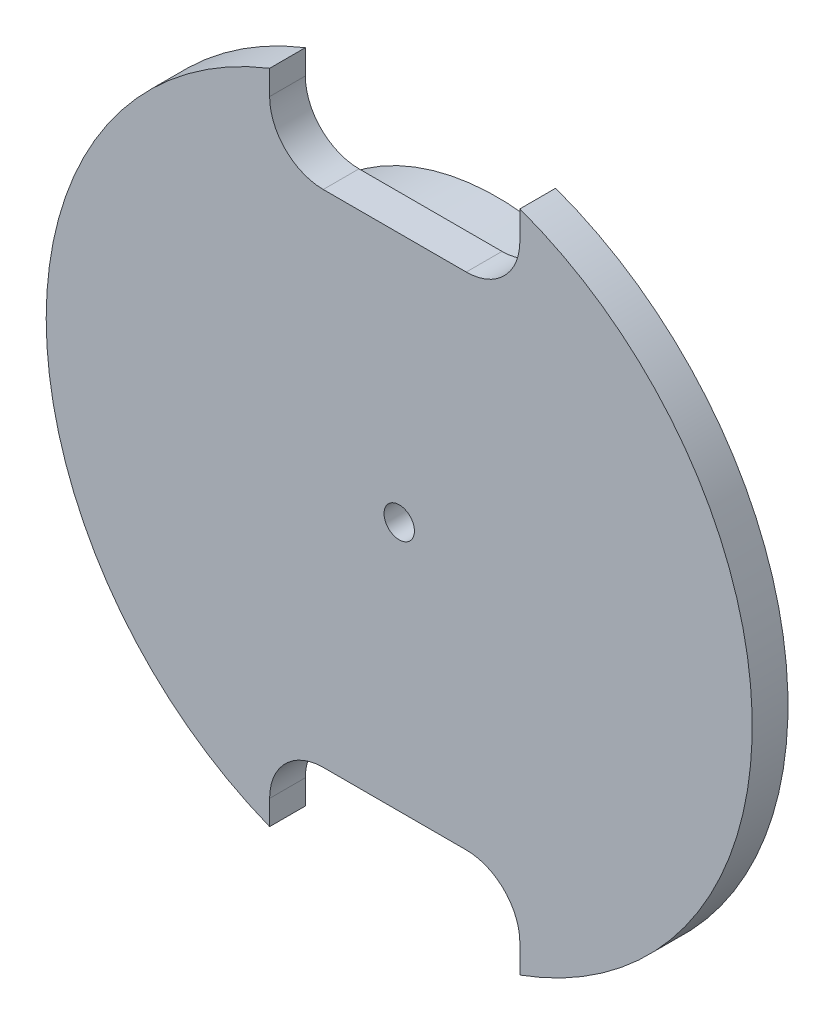
SolidWorks part; units mm, degrees
ref_plane "Płaszczyzna przednia" through (0, 0, 0) normal (0, 0, 1) x (1, 0, 0)
ref_plane "Płaszczyzna górna" through (0, 0, 0) normal (0, 1, 0) x (1, 0, 0)
ref_plane "Płaszczyzna prawa" through (0, 0, 0) normal (1, 0, 0) x (0, 0, -1)
sketch "Sketch1" plane through (0, 0, 0) normal (0, 0, 1) x (1, 0, 0)
  circle A0 centre (-12.8255, 19.2383) radius 39.5
extrude "Boss-Extrude1" add sketch "Sketch1" along normal blind 4
sketch "Sketch3" plane through (0, 0, 4) normal (0, 0, 1) x (1, 0, 0)
  circle A0 centre (-12.8255, 19.2383) radius 35
sketch "Sketch6" plane through (0, 0, 4) normal (0, 0, 1) x (1, 0, 0)
  line L0 (-12.8255, 54.2383) -> (-12.8255, -15.7617)
  line L1 (-47.8255, 19.2383) -> (22.1745, 19.2383)
  circle A0 centre (-12.8255, 19.2383) radius 35 construction
sketch "Sketch5" plane through (0, 0, 4) normal (0, 0, 1) x (1, 0, 0)
  line L0 (-21.3255, 59.2383) -> (-5.3255, 59.2383)
  line L1 (-21.3255, -8.7617) -> (-5.3255, -8.7617)
  line L2 (-21.3255, -8.7617) -> (-21.3255, -20.7617)
  line L3 (-21.3255, -20.7617) -> (-5.3255, -20.7617)
  line L4 (-5.3255, -8.7617) -> (-5.3255, -20.7617)
  line L5 (-21.3255, 59.2383) -> (-21.3255, 47.2383)
  line L6 (-21.3255, 47.2383) -> (-5.3255, 47.2383)
  line L7 (-5.3255, 59.2383) -> (-5.3255, 47.2383)
  line L17 (-12.8255, 54.2383) -> (-12.8255, -15.7617) construction
  line L22 (-27.3255, -14.7617) -> (-27.3255, -23.8497)
  line L23 (-27.3255, -23.8497) -> (0.6745, -23.8497)
  line L24 (0.6745, -23.8497) -> (0.6745, -14.7617)
  line L25 (0.6745, -14.7617) -> (-27.3255, -14.7617)
  line L30 (-27.3255, 53.2383) -> (-27.3255, 65.055)
  line L31 (-27.3255, 65.055) -> (0.6745, 65.055)
  line L32 (0.6745, 65.055) -> (0.6745, 53.2383)
  line L33 (0.6745, 53.2383) -> (-27.3255, 53.2383)
  arc A0 (-5.3255, -8.7617) -> (-5.3255, -20.7617) centre (-5.3255, -14.7617) cw
  arc A1 (-21.3255, -8.7617) -> (-21.3255, -20.7617) centre (-21.3255, -14.7617) ccw
  arc A2 (-5.3255, 59.2383) -> (-5.3255, 47.2383) centre (-5.3255, 53.2383) cw
  arc A3 (-21.3255, 59.2383) -> (-21.3255, 47.2383) centre (-21.3255, 53.2383) ccw
  circle A8 centre (-12.8255, 19.2383) radius 39.5 construction
  dimension "D1" = 16
  dimension "D2" = 12
  dimension "D3" = 16
  dimension "D4" = 12
  dimension "D10" = 40
  dimension "D12" = 40
  dimension "D13" = 7.5
  dimension "D15" = 7.5
extrude "Cut-Extrude2" cut sketch "Sketch5" against normal blind 10 contours A2 L7 | L5 A3 | L2 A1 | L4 L1 L2 L3 | A0 L4 | L7 L33 L5 L6 | L33 L30 L31 L32 | L25 L22 L23 L24 region at (-13.3255, 50.2383, 4) region at (-23.872, 50.6918, 4) region at (-2.7791, 50.6918, 4) region at (-13.3255, -11.7617, 4) region at (-23.872, -12.2152, 4) region at (-2.7791, -12.2152, 4)
sketch "Sketch7" plane through (0, 0, 0) normal (0, 0, -1) x (-1, 0, 0)
  circle A0 centre (12.8255, 19.2383) radius 26
extrude "Boss-Extrude2" add sketch "Sketch7" along normal blind 7
sketch "Sketch8" plane through (0, 0, -7) normal (0, 0, -1) x (-1, 0, 0)
  circle A0 centre (12.8255, 19.2383) radius 1.7
extrude "Cut-Extrude3" cut sketch "Sketch8" against normal blind 20
sketch "Sketch9" plane through (0, 0, -7) normal (0, 0, -1) x (-1, 0, 0)
  circle A0 centre (12.8255, 19.2383) radius 5
extrude "Cut-Extrude4" cut sketch "Sketch9" against normal blind 4
